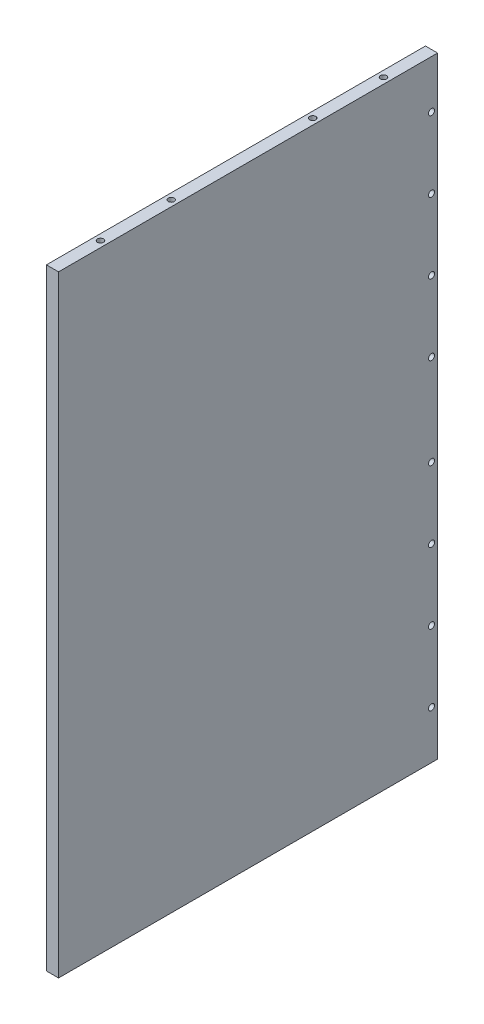
SolidWorks part; units mm, degrees
ref_plane "Alzado" through (0, 0, 0) normal (0, 0, 1) x (1, 0, 0)
ref_plane "Planta" through (0, 0, 0) normal (0, 1, 0) x (1, 0, 0)
ref_plane "Vista lateral" through (0, 0, 0) normal (1, 0, 0) x (0, 0, -1)
sketch "Croquis2" plane through (0, 0, 0) normal (1, 0, 0) x (0, 0, -1)
  line L1 (-187.5, 302.5) -> (187.5, 302.5)
  line L2 (-187.5, 302.5) -> (-187.5, -302.5)
  line L3 (-187.5, -302.5) -> (187.5, -302.5)
  line L4 (187.5, 302.5) -> (187.5, -302.5)
  dimension "D1" = 375
  dimension "D2" = 605
  dimension "D3" = 302.5
  dimension "D4" = 187.5
extrude "Saliente-Extruir1" add sketch "Croquis2" along normal mid plane 12
sketch "Croquis3" plane through (0, 302.5, 0) normal (0, 1, 0) x (1, 0, 0)
  line L0 (0, 187.5) -> (0, -187.5) construction
  line L1 (6, 187.5) -> (-6, 187.5) construction
  line L2 (6, -187.5) -> (-6, -187.5) construction
  line L3 (-6, 0) -> (6, 0) construction
  line L4 (-6, 187.5) -> (-6, -187.5) construction
  line L5 (6, 187.5) -> (6, -187.5) construction
  circle A0 centre (0, 140) radius 3
  circle A1 centre (0, 70) radius 3
  circle A2 centre (0, -70) radius 3
  circle A3 centre (0, -140) radius 3
  dimension "D1" = 47.5
  dimension "D2" = 2
extrude "Cortar-Extruir1" cut sketch "Croquis3" against normal blind 23
mirror "Simetría1" about plane through (0, 0, 0) normal (0, 1, 0) of "Cortar-Extruir1"
sketch "Croquis6" plane through (6, 0, 0) normal (1, 0, 0) x (0, 0, -1)
  line L0 (181.5, 302.5) -> (181.5, -302.5) construction
  line L1 (187.5, 302.5) -> (-187.5, 302.5) construction
  line L2 (-187.5, -302.5) -> (187.5, -302.5) construction
  line L3 (187.5, -302.5) -> (187.5, 302.5) construction
  line L4 (-187.5, 0) -> (187.5, 0) construction
  line L5 (-187.5, 302.5) -> (-187.5, -302.5) construction
  circle A0 centre (181.5, -255) radius 3
  circle A1 centre (181.5, -185) radius 3
  circle A2 centre (181.5, -115) radius 3
  circle A3 centre (181.5, -45) radius 3
  circle A4 centre (181.5, 45) radius 3
  circle A5 centre (181.5, 115) radius 3
  circle A6 centre (181.5, 185) radius 3
  circle A7 centre (181.5, 255) radius 3
  dimension "D2" = 47.5
  dimension "D1" = 6
  dimension "D3" = 4
extrude "Cortar-Extruir2" cut sketch "Croquis6" against normal blind 5
